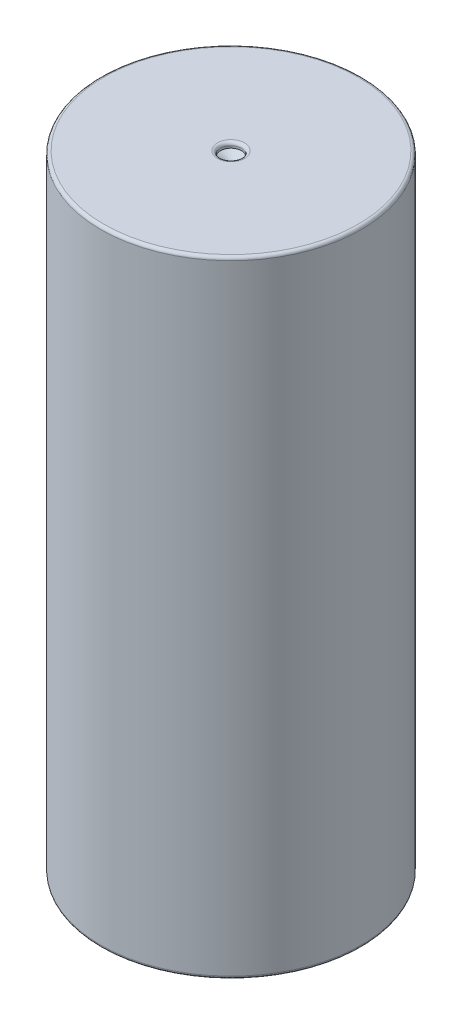
SolidWorks part; units mm, degrees
ref_plane "Front Plane" through (0, 0, 0) normal (0, 0, 1) x (1, 0, 0)
ref_plane "Top Plane" through (0, 0, 0) normal (0, 1, 0) x (1, 0, 0)
ref_plane "Right Plane" through (0, 0, 0) normal (1, 0, 0) x (0, 0, -1)
sketch "Sketch2" plane through (0, 0, 0) normal (0, 0, 1) x (1, 0, 0)
  line L5 (12.5, 30) -> (0, 30)
  line L6 (12.5, 30) -> (12.5, -30)
  line L7 (12.5, -30) -> (0, -30)
  line L8 (0, 30) -> (0, -30)
  line L9 (12.5, 30) -> (0, -30) construction
  line L10 (12.5, -30) -> (0, 30) construction
  point P0 (6.25, 0)
  dimension "D1" = 12.5
  dimension "D2" = 60
revolve "Revolve1" add sketch "Sketch2" angle 360 about L8
sketch "Sketch4" plane through (0, 0, 0) normal (0, 0, 1) x (1, 0, 0)
  line L0 (0, 30) -> (0, 29)
  line L1 (12.5, 30) -> (-12.5, 30) construction
  line L2 (0, 29) -> (1, 29.5)
  line L3 (1, 29.5) -> (1, 30)
  line L4 (1, 30) -> (0, 30)
  dimension "D1" = 1
  dimension "D2" = 1
  dimension "D3" = 0.5
revolve "Cut-Revolve1" cut sketch "Sketch4" angle 360 about L0
mirror "Mirror2" about plane through (0, 0, 0) normal (0, 1, 0) of "Cut-Revolve1"
fillet "Fillet1" radius 0.3 4 edges at (0, 30, 12.5) (-1, 30, 0) (0, -30, 12.5) (-1, -30, 0)
ref_axis "Axis1" through (0, -29.7, 0) along (0, 1, 0)
